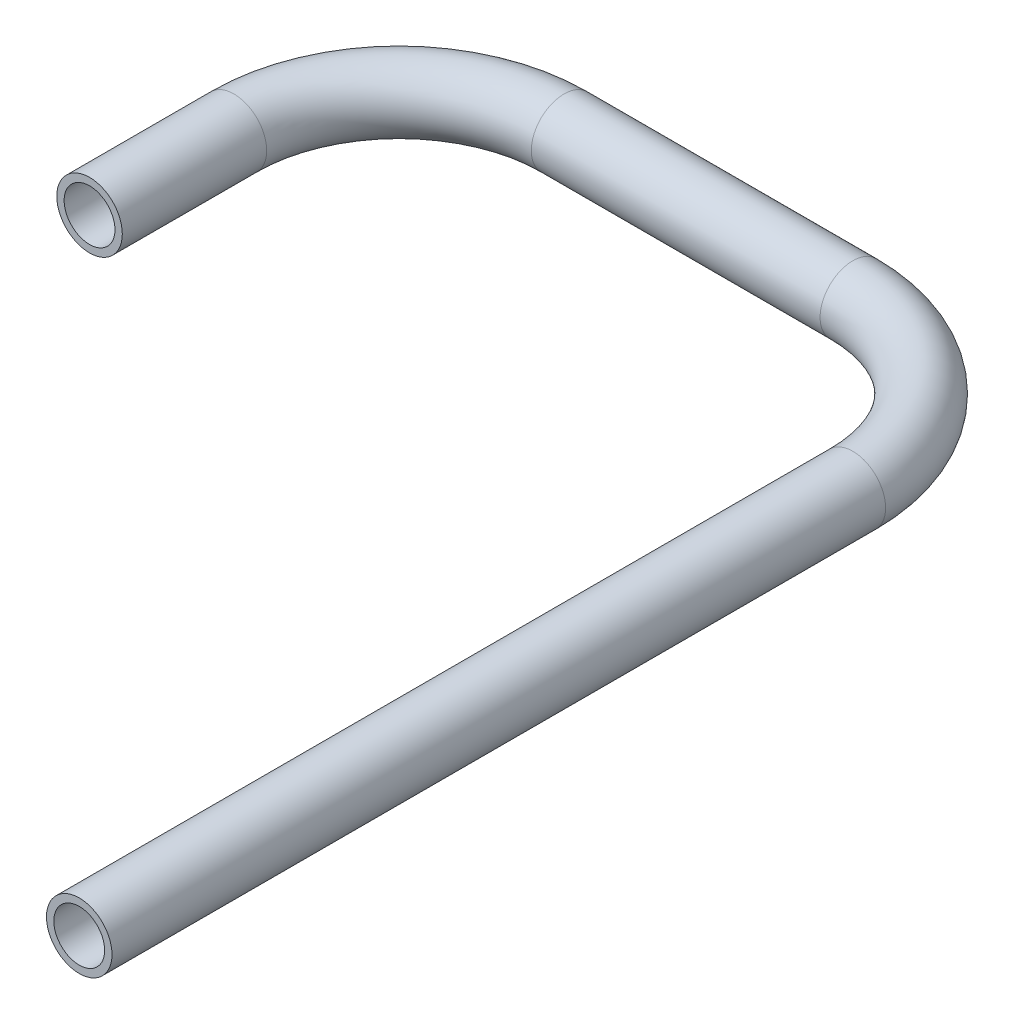
SolidWorks part; units mm, degrees
ref_plane "Front Plane" through (0, 0, 0) normal (0, 0, 1) x (1, 0, 0)
ref_plane "Top Plane" through (0, 0, 0) normal (0, 1, 0) x (1, 0, 0)
ref_plane "Right Plane" through (0, 0, 0) normal (1, 0, 0) x (0, 0, -1)
sketch "Sketch1" plane through (0, 0, 0) normal (0, 1, 0) x (1, 0, 0)
  line L0 (0, 0) -> (0, 14)
  line L1 (16, 30) -> (44, 30)
  line L2 (60, 14) -> (60, -61)
  arc A0 (44, 30) -> (60, 14) centre (44, 14) cw
  arc A1 (0, 14) -> (16, 30) centre (16, 14) cw
  dimension "D1" = 16
  dimension "D2" = 16
  dimension "D3" = 14
  dimension "D4" = 75
  dimension "D5" = 60
sketch "Sketch2" plane through (0, 0, 0) normal (0, 0, 1) x (1, 0, 0)
  circle A0 centre (0, 0) radius 3.175
  dimension "D1" = 6.35
sweep "Sweep-Thin1" add profiles "Sketch2" path "Sketch1" parameters "D1"=0.7112
